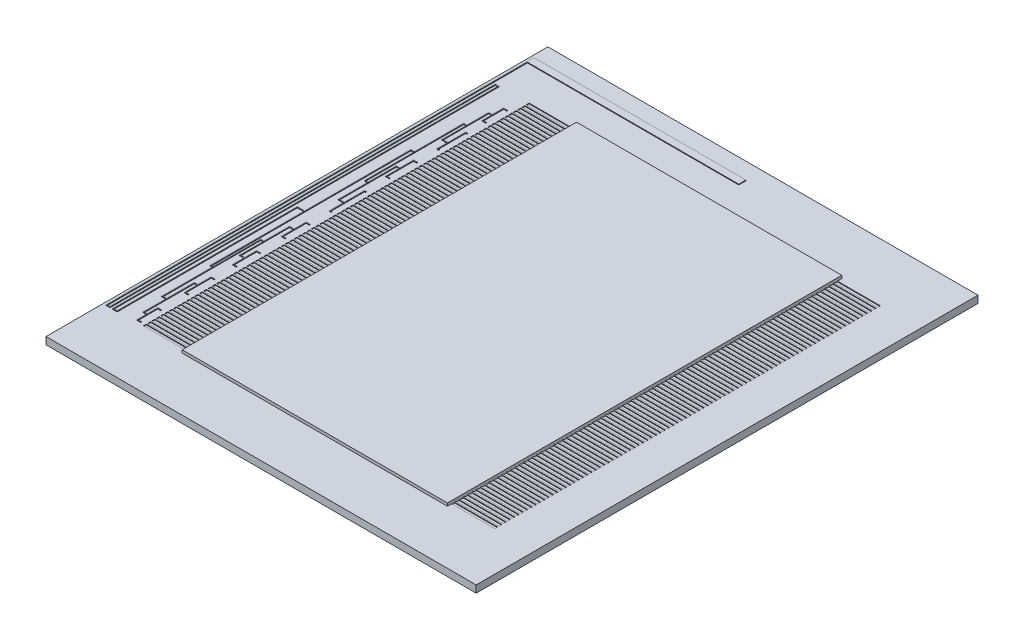
SolidWorks part; units mm, degrees
ref_plane "Front Plane" through (0, 0, 0) normal (0, 0, 1) x (1, 0, 0)
ref_plane "Top Plane" through (0, 0, 0) normal (0, 1, 0) x (1, 0, 0)
ref_plane "Right Plane" through (0, 0, 0) normal (1, 0, 0) x (0, 0, -1)
sketch "Sketch2" plane through (0, 0, 0) normal (0, 1, 0) x (1, 0, 0)
  line L1 (-15, 17.5) -> (15, 17.5)
  line L2 (-15, 17.5) -> (-15, -17.5)
  line L3 (-15, -17.5) -> (15, -17.5)
  line L4 (15, 17.5) -> (15, -17.5)
  line L5 (-15, 17.5) -> (15, -17.5) construction
  line L6 (-15, -17.5) -> (15, 17.5) construction
  point P0 (0, 0)
  dimension "D1" = 35
  dimension "D2" = 30
extrude "Boss-Extrude1" add sketch "Sketch2" against normal blind 0.5
sketch "Sketch3" plane through (0, 0, 0) normal (0, 1, 0) x (1, 0, 0)
  line L1 (-9.25, 13.75) -> (9.25, 13.75)
  line L2 (-9.25, 13.75) -> (-9.25, -13.75)
  line L3 (-9.25, -13.75) -> (9.25, -13.75)
  line L4 (9.25, 13.75) -> (9.25, -13.75)
  line L5 (-9.25, 13.75) -> (9.25, -13.75) construction
  line L6 (-9.25, -13.75) -> (9.25, 13.75) construction
  point P0 (0, 0)
  dimension "D1" = 18.5
  dimension "D2" = 27.5
sketch "Sketch4" plane through (0, 0, 0) normal (0, 1, 0) x (1, 0, 0)
  line L0 (9.25, 13.45) -> (9.25, 13.25)
  line L1 (9.25, 13.45) -> (12.25, 13.45)
  line L2 (9.25, 13.25) -> (12.25, 13.25)
  line L3 (12.25, 13.45) -> (12.25, 13.25)
  line L4 (9.25, 13.75) -> (9.25, -13.75) construction
  line L5 (9.25, 13.15) -> (9.25, 12.95)
  line L6 (9.25, 13.15) -> (12.25, 13.15)
  line L7 (12.25, 13.15) -> (12.25, 12.95)
  line L8 (9.25, 12.95) -> (12.25, 12.95)
  line L9 (9.25, 12.85) -> (9.25, 12.65)
  line L10 (9.25, 12.85) -> (12.25, 12.85)
  line L11 (12.25, 12.85) -> (12.25, 12.65)
  line L12 (9.25, 12.65) -> (12.25, 12.65)
  line L13 (9.25, 12.55) -> (9.25, 12.35)
  line L14 (9.25, 12.55) -> (12.25, 12.55)
  line L15 (12.25, 12.55) -> (12.25, 12.35)
  line L16 (9.25, 12.35) -> (12.25, 12.35)
  line L17 (9.25, 12.25) -> (9.25, 12.05)
  line L18 (9.25, 12.25) -> (12.25, 12.25)
  line L19 (12.25, 12.25) -> (12.25, 12.05)
  line L20 (9.25, 12.05) -> (12.25, 12.05)
  line L21 (9.25, 11.95) -> (9.25, 11.75)
  line L22 (9.25, 11.95) -> (12.25, 11.95)
  line L23 (12.25, 11.95) -> (12.25, 11.75)
  line L24 (9.25, 11.75) -> (12.25, 11.75)
  line L25 (9.25, 11.65) -> (9.25, 11.45)
  line L26 (9.25, 11.65) -> (12.25, 11.65)
  line L27 (12.25, 11.65) -> (12.25, 11.45)
  line L28 (9.25, 11.45) -> (12.25, 11.45)
  line L29 (9.25, 11.35) -> (9.25, 11.15)
  line L30 (9.25, 11.35) -> (12.25, 11.35)
  line L31 (12.25, 11.35) -> (12.25, 11.15)
  line L32 (9.25, 11.15) -> (12.25, 11.15)
  line L33 (9.25, 11.05) -> (9.25, 10.85)
  line L34 (9.25, 11.05) -> (12.25, 11.05)
  line L35 (12.25, 11.05) -> (12.25, 10.85)
  line L36 (9.25, 10.85) -> (12.25, 10.85)
  line L37 (9.25, 10.75) -> (9.25, 10.55)
  line L38 (9.25, 10.75) -> (12.25, 10.75)
  line L39 (12.25, 10.75) -> (12.25, 10.55)
  line L40 (9.25, 10.55) -> (12.25, 10.55)
  line L41 (9.25, 10.45) -> (9.25, 10.25)
  line L42 (9.25, 10.45) -> (12.25, 10.45)
  line L43 (12.25, 10.45) -> (12.25, 10.25)
  line L44 (9.25, 10.25) -> (12.25, 10.25)
  line L45 (9.25, 10.15) -> (9.25, 9.95)
  line L46 (9.25, 10.15) -> (12.25, 10.15)
  line L47 (12.25, 10.15) -> (12.25, 9.95)
  line L48 (9.25, 9.95) -> (12.25, 9.95)
  line L49 (9.25, 9.85) -> (9.25, 9.65)
  line L50 (9.25, 9.85) -> (12.25, 9.85)
  line L51 (12.25, 9.85) -> (12.25, 9.65)
  line L52 (9.25, 9.65) -> (12.25, 9.65)
  line L53 (9.25, 9.55) -> (9.25, 9.35)
  line L54 (9.25, 9.55) -> (12.25, 9.55)
  line L55 (12.25, 9.55) -> (12.25, 9.35)
  line L56 (9.25, 9.35) -> (12.25, 9.35)
  line L57 (9.25, 9.25) -> (9.25, 9.05)
  line L58 (9.25, 9.25) -> (12.25, 9.25)
  line L59 (12.25, 9.25) -> (12.25, 9.05)
  line L60 (9.25, 9.05) -> (12.25, 9.05)
  line L61 (9.25, 8.95) -> (9.25, 8.75)
  line L62 (9.25, 8.95) -> (12.25, 8.95)
  line L63 (12.25, 8.95) -> (12.25, 8.75)
  line L64 (9.25, 8.75) -> (12.25, 8.75)
  line L65 (9.25, 8.65) -> (9.25, 8.45)
  line L66 (9.25, 8.65) -> (12.25, 8.65)
  line L67 (12.25, 8.65) -> (12.25, 8.45)
  line L68 (9.25, 8.45) -> (12.25, 8.45)
  line L69 (9.25, 8.35) -> (9.25, 8.15)
  line L70 (9.25, 8.35) -> (12.25, 8.35)
  line L71 (12.25, 8.35) -> (12.25, 8.15)
  line L72 (9.25, 8.15) -> (12.25, 8.15)
  line L73 (9.25, 8.05) -> (9.25, 7.85)
  line L74 (9.25, 8.05) -> (12.25, 8.05)
  line L75 (12.25, 8.05) -> (12.25, 7.85)
  line L76 (9.25, 7.85) -> (12.25, 7.85)
  line L77 (9.25, 7.75) -> (9.25, 7.55)
  line L78 (9.25, 7.75) -> (12.25, 7.75)
  line L79 (12.25, 7.75) -> (12.25, 7.55)
  line L80 (9.25, 7.55) -> (12.25, 7.55)
  line L81 (9.25, 7.45) -> (9.25, 7.25)
  line L82 (9.25, 7.45) -> (12.25, 7.45)
  line L83 (12.25, 7.45) -> (12.25, 7.25)
  line L84 (9.25, 7.25) -> (12.25, 7.25)
  line L85 (9.25, 7.15) -> (9.25, 6.95)
  line L86 (9.25, 7.15) -> (12.25, 7.15)
  line L87 (12.25, 7.15) -> (12.25, 6.95)
  line L88 (9.25, 6.95) -> (12.25, 6.95)
  line L89 (9.25, 6.85) -> (9.25, 6.65)
  line L90 (9.25, 6.85) -> (12.25, 6.85)
  line L91 (12.25, 6.85) -> (12.25, 6.65)
  line L92 (9.25, 6.65) -> (12.25, 6.65)
  line L93 (9.25, 6.55) -> (9.25, 6.35)
  line L94 (9.25, 6.55) -> (12.25, 6.55)
  line L95 (12.25, 6.55) -> (12.25, 6.35)
  line L96 (9.25, 6.35) -> (12.25, 6.35)
  line L97 (9.25, 6.25) -> (9.25, 6.05)
  line L98 (9.25, 6.25) -> (12.25, 6.25)
  line L99 (12.25, 6.25) -> (12.25, 6.05)
  line L100 (9.25, 6.05) -> (12.25, 6.05)
  line L101 (9.25, 5.95) -> (9.25, 5.75)
  line L102 (9.25, 5.95) -> (12.25, 5.95)
  line L103 (12.25, 5.95) -> (12.25, 5.75)
  line L104 (9.25, 5.75) -> (12.25, 5.75)
  line L105 (9.25, 5.65) -> (9.25, 5.45)
  line L106 (9.25, 5.65) -> (12.25, 5.65)
  line L107 (12.25, 5.65) -> (12.25, 5.45)
  line L108 (9.25, 5.45) -> (12.25, 5.45)
  line L109 (9.25, 5.35) -> (9.25, 5.15)
  line L110 (9.25, 5.35) -> (12.25, 5.35)
  line L111 (12.25, 5.35) -> (12.25, 5.15)
  line L112 (9.25, 5.15) -> (12.25, 5.15)
  line L113 (9.25, 5.05) -> (9.25, 4.85)
  line L114 (9.25, 5.05) -> (12.25, 5.05)
  line L115 (12.25, 5.05) -> (12.25, 4.85)
  line L116 (9.25, 4.85) -> (12.25, 4.85)
  line L117 (9.25, 4.75) -> (9.25, 4.55)
  line L118 (9.25, 4.75) -> (12.25, 4.75)
  line L119 (12.25, 4.75) -> (12.25, 4.55)
  line L120 (9.25, 4.55) -> (12.25, 4.55)
  line L121 (9.25, 4.45) -> (9.25, 4.25)
  line L122 (9.25, 4.45) -> (12.25, 4.45)
  line L123 (12.25, 4.45) -> (12.25, 4.25)
  line L124 (9.25, 4.25) -> (12.25, 4.25)
  line L125 (9.25, 4.15) -> (9.25, 3.95)
  line L126 (9.25, 4.15) -> (12.25, 4.15)
  line L127 (12.25, 4.15) -> (12.25, 3.95)
  line L128 (9.25, 3.95) -> (12.25, 3.95)
  line L129 (9.25, 3.85) -> (9.25, 3.65)
  line L130 (9.25, 3.85) -> (12.25, 3.85)
  line L131 (12.25, 3.85) -> (12.25, 3.65)
  line L132 (9.25, 3.65) -> (12.25, 3.65)
  line L133 (9.25, 3.55) -> (9.25, 3.35)
  line L134 (9.25, 3.55) -> (12.25, 3.55)
  line L135 (12.25, 3.55) -> (12.25, 3.35)
  line L136 (9.25, 3.35) -> (12.25, 3.35)
  line L137 (9.25, 3.25) -> (9.25, 3.05)
  line L138 (9.25, 3.25) -> (12.25, 3.25)
  line L139 (12.25, 3.25) -> (12.25, 3.05)
  line L140 (9.25, 3.05) -> (12.25, 3.05)
  line L141 (9.25, 2.95) -> (9.25, 2.75)
  line L142 (9.25, 2.95) -> (12.25, 2.95)
  line L143 (12.25, 2.95) -> (12.25, 2.75)
  line L144 (9.25, 2.75) -> (12.25, 2.75)
  line L145 (9.25, 2.65) -> (9.25, 2.45)
  line L146 (9.25, 2.65) -> (12.25, 2.65)
  line L147 (12.25, 2.65) -> (12.25, 2.45)
  line L148 (9.25, 2.45) -> (12.25, 2.45)
  line L149 (9.25, 2.35) -> (9.25, 2.15)
  line L150 (9.25, 2.35) -> (12.25, 2.35)
  line L151 (12.25, 2.35) -> (12.25, 2.15)
  line L152 (9.25, 2.15) -> (12.25, 2.15)
  line L153 (9.25, 2.05) -> (9.25, 1.85)
  line L154 (9.25, 2.05) -> (12.25, 2.05)
  line L155 (12.25, 2.05) -> (12.25, 1.85)
  line L156 (9.25, 1.85) -> (12.25, 1.85)
  line L157 (9.25, 1.75) -> (9.25, 1.55)
  line L158 (9.25, 1.75) -> (12.25, 1.75)
  line L159 (12.25, 1.75) -> (12.25, 1.55)
  line L160 (9.25, 1.55) -> (12.25, 1.55)
  line L161 (9.25, 1.45) -> (9.25, 1.25)
  line L162 (9.25, 1.45) -> (12.25, 1.45)
  line L163 (12.25, 1.45) -> (12.25, 1.25)
  line L164 (9.25, 1.25) -> (12.25, 1.25)
  line L165 (9.25, 1.15) -> (9.25, 0.95)
  line L166 (9.25, 1.15) -> (12.25, 1.15)
  line L167 (12.25, 1.15) -> (12.25, 0.95)
  line L168 (9.25, 0.95) -> (12.25, 0.95)
  line L169 (9.25, 0.85) -> (9.25, 0.65)
  line L170 (9.25, 0.85) -> (12.25, 0.85)
  line L171 (12.25, 0.85) -> (12.25, 0.65)
  line L172 (9.25, 0.65) -> (12.25, 0.65)
  line L173 (9.25, 0.55) -> (9.25, 0.35)
  line L174 (9.25, 0.55) -> (12.25, 0.55)
  line L175 (12.25, 0.55) -> (12.25, 0.35)
  line L176 (9.25, 0.35) -> (12.25, 0.35)
  line L177 (9.25, 0.25) -> (9.25, 0.05)
  line L178 (9.25, 0.25) -> (12.25, 0.25)
  line L179 (12.25, 0.25) -> (12.25, 0.05)
  line L180 (9.25, 0.05) -> (12.25, 0.05)
  line L181 (9.25, -0.05) -> (9.25, -0.25)
  line L182 (9.25, -0.05) -> (12.25, -0.05)
  line L183 (12.25, -0.05) -> (12.25, -0.25)
  line L184 (9.25, -0.25) -> (12.25, -0.25)
  line L185 (9.25, -0.35) -> (9.25, -0.55)
  line L186 (9.25, -0.35) -> (12.25, -0.35)
  line L187 (12.25, -0.35) -> (12.25, -0.55)
  line L188 (9.25, -0.55) -> (12.25, -0.55)
  line L189 (9.25, -0.65) -> (9.25, -0.85)
  line L190 (9.25, -0.65) -> (12.25, -0.65)
  line L191 (12.25, -0.65) -> (12.25, -0.85)
  line L192 (9.25, -0.85) -> (12.25, -0.85)
  line L193 (9.25, -0.95) -> (9.25, -1.15)
  line L194 (9.25, -0.95) -> (12.25, -0.95)
  line L195 (12.25, -0.95) -> (12.25, -1.15)
  line L196 (9.25, -1.15) -> (12.25, -1.15)
  line L197 (9.25, -1.25) -> (9.25, -1.45)
  line L198 (9.25, -1.25) -> (12.25, -1.25)
  line L199 (12.25, -1.25) -> (12.25, -1.45)
  line L200 (9.25, -1.45) -> (12.25, -1.45)
  line L201 (9.25, -1.55) -> (9.25, -1.75)
  line L202 (9.25, -1.55) -> (12.25, -1.55)
  line L203 (12.25, -1.55) -> (12.25, -1.75)
  line L204 (9.25, -1.75) -> (12.25, -1.75)
  line L205 (9.25, -1.85) -> (9.25, -2.05)
  line L206 (9.25, -1.85) -> (12.25, -1.85)
  line L207 (12.25, -1.85) -> (12.25, -2.05)
  line L208 (9.25, -2.05) -> (12.25, -2.05)
  line L209 (9.25, -2.15) -> (9.25, -2.35)
  line L210 (9.25, -2.15) -> (12.25, -2.15)
  line L211 (12.25, -2.15) -> (12.25, -2.35)
  line L212 (9.25, -2.35) -> (12.25, -2.35)
  line L213 (9.25, -2.45) -> (9.25, -2.65)
  line L214 (9.25, -2.45) -> (12.25, -2.45)
  line L215 (12.25, -2.45) -> (12.25, -2.65)
  line L216 (9.25, -2.65) -> (12.25, -2.65)
  line L217 (9.25, -2.75) -> (9.25, -2.95)
  line L218 (9.25, -2.75) -> (12.25, -2.75)
  line L219 (12.25, -2.75) -> (12.25, -2.95)
  line L220 (9.25, -2.95) -> (12.25, -2.95)
  line L221 (9.25, -3.05) -> (9.25, -3.25)
  line L222 (9.25, -3.05) -> (12.25, -3.05)
  line L223 (12.25, -3.05) -> (12.25, -3.25)
  line L224 (9.25, -3.25) -> (12.25, -3.25)
  line L225 (9.25, -3.35) -> (9.25, -3.55)
  line L226 (9.25, -3.35) -> (12.25, -3.35)
  line L227 (12.25, -3.35) -> (12.25, -3.55)
  line L228 (9.25, -3.55) -> (12.25, -3.55)
  line L229 (9.25, -3.65) -> (9.25, -3.85)
  line L230 (9.25, -3.65) -> (12.25, -3.65)
  line L231 (12.25, -3.65) -> (12.25, -3.85)
  line L232 (9.25, -3.85) -> (12.25, -3.85)
  line L233 (9.25, -3.95) -> (9.25, -4.15)
  line L234 (9.25, -3.95) -> (12.25, -3.95)
  line L235 (12.25, -3.95) -> (12.25, -4.15)
  line L236 (9.25, -4.15) -> (12.25, -4.15)
  line L237 (9.25, -4.25) -> (9.25, -4.45)
  line L238 (9.25, -4.25) -> (12.25, -4.25)
  line L239 (12.25, -4.25) -> (12.25, -4.45)
  line L240 (9.25, -4.45) -> (12.25, -4.45)
  line L241 (9.25, -4.55) -> (9.25, -4.75)
  line L242 (9.25, -4.55) -> (12.25, -4.55)
  line L243 (12.25, -4.55) -> (12.25, -4.75)
  line L244 (9.25, -4.75) -> (12.25, -4.75)
  line L245 (9.25, -4.85) -> (9.25, -5.05)
  line L246 (9.25, -4.85) -> (12.25, -4.85)
  line L247 (12.25, -4.85) -> (12.25, -5.05)
  line L248 (9.25, -5.05) -> (12.25, -5.05)
  line L249 (9.25, -5.15) -> (9.25, -5.35)
  line L250 (9.25, -5.15) -> (12.25, -5.15)
  line L251 (12.25, -5.15) -> (12.25, -5.35)
  line L252 (9.25, -5.35) -> (12.25, -5.35)
  line L253 (9.25, -5.45) -> (9.25, -5.65)
  line L254 (9.25, -5.45) -> (12.25, -5.45)
  line L255 (12.25, -5.45) -> (12.25, -5.65)
  line L256 (9.25, -5.65) -> (12.25, -5.65)
  line L257 (9.25, -5.75) -> (9.25, -5.95)
  line L258 (9.25, -5.75) -> (12.25, -5.75)
  line L259 (12.25, -5.75) -> (12.25, -5.95)
  line L260 (9.25, -5.95) -> (12.25, -5.95)
  line L261 (9.25, -6.05) -> (9.25, -6.25)
  line L262 (9.25, -6.05) -> (12.25, -6.05)
  line L263 (12.25, -6.05) -> (12.25, -6.25)
  line L264 (9.25, -6.25) -> (12.25, -6.25)
  line L265 (9.25, -6.35) -> (9.25, -6.55)
  line L266 (9.25, -6.35) -> (12.25, -6.35)
  line L267 (12.25, -6.35) -> (12.25, -6.55)
  line L268 (9.25, -6.55) -> (12.25, -6.55)
  line L269 (9.25, -6.65) -> (9.25, -6.85)
  line L270 (9.25, -6.65) -> (12.25, -6.65)
  line L271 (12.25, -6.65) -> (12.25, -6.85)
  line L272 (9.25, -6.85) -> (12.25, -6.85)
  line L273 (9.25, -6.95) -> (9.25, -7.15)
  line L274 (9.25, -6.95) -> (12.25, -6.95)
  line L275 (12.25, -6.95) -> (12.25, -7.15)
  line L276 (9.25, -7.15) -> (12.25, -7.15)
  line L277 (9.25, -7.25) -> (9.25, -7.45)
  line L278 (9.25, -7.25) -> (12.25, -7.25)
  line L279 (12.25, -7.25) -> (12.25, -7.45)
  line L280 (9.25, -7.45) -> (12.25, -7.45)
  line L281 (9.25, -7.55) -> (9.25, -7.75)
  line L282 (9.25, -7.55) -> (12.25, -7.55)
  line L283 (12.25, -7.55) -> (12.25, -7.75)
  line L284 (9.25, -7.75) -> (12.25, -7.75)
  line L285 (9.25, -7.85) -> (9.25, -8.05)
  line L286 (9.25, -7.85) -> (12.25, -7.85)
  line L287 (12.25, -7.85) -> (12.25, -8.05)
  line L288 (9.25, -8.05) -> (12.25, -8.05)
  line L289 (9.25, -8.15) -> (9.25, -8.35)
  line L290 (9.25, -8.15) -> (12.25, -8.15)
  line L291 (12.25, -8.15) -> (12.25, -8.35)
  line L292 (9.25, -8.35) -> (12.25, -8.35)
  line L293 (9.25, -8.45) -> (9.25, -8.65)
  line L294 (9.25, -8.45) -> (12.25, -8.45)
  line L295 (12.25, -8.45) -> (12.25, -8.65)
  line L296 (9.25, -8.65) -> (12.25, -8.65)
  line L297 (9.25, -8.75) -> (9.25, -8.95)
  line L298 (9.25, -8.75) -> (12.25, -8.75)
  line L299 (12.25, -8.75) -> (12.25, -8.95)
  line L300 (9.25, -8.95) -> (12.25, -8.95)
  line L301 (9.25, -9.05) -> (9.25, -9.25)
  line L302 (9.25, -9.05) -> (12.25, -9.05)
  line L303 (12.25, -9.05) -> (12.25, -9.25)
  line L304 (9.25, -9.25) -> (12.25, -9.25)
  line L305 (9.25, -9.35) -> (9.25, -9.55)
  line L306 (9.25, -9.35) -> (12.25, -9.35)
  line L307 (12.25, -9.35) -> (12.25, -9.55)
  line L308 (9.25, -9.55) -> (12.25, -9.55)
  line L309 (9.25, -9.65) -> (9.25, -9.85)
  line L310 (9.25, -9.65) -> (12.25, -9.65)
  line L311 (12.25, -9.65) -> (12.25, -9.85)
  line L312 (9.25, -9.85) -> (12.25, -9.85)
  line L313 (9.25, -9.95) -> (9.25, -10.15)
  line L314 (9.25, -9.95) -> (12.25, -9.95)
  line L315 (12.25, -9.95) -> (12.25, -10.15)
  line L316 (9.25, -10.15) -> (12.25, -10.15)
  line L317 (9.25, -10.25) -> (9.25, -10.45)
  line L318 (9.25, -10.25) -> (12.25, -10.25)
  line L319 (12.25, -10.25) -> (12.25, -10.45)
  line L320 (9.25, -10.45) -> (12.25, -10.45)
  line L321 (9.25, -10.55) -> (9.25, -10.75)
  line L322 (9.25, -10.55) -> (12.25, -10.55)
  line L323 (12.25, -10.55) -> (12.25, -10.75)
  line L324 (9.25, -10.75) -> (12.25, -10.75)
  line L325 (9.25, -10.85) -> (9.25, -11.05)
  line L326 (9.25, -10.85) -> (12.25, -10.85)
  line L327 (12.25, -10.85) -> (12.25, -11.05)
  line L328 (9.25, -11.05) -> (12.25, -11.05)
  line L329 (9.25, -11.15) -> (9.25, -11.35)
  line L330 (9.25, -11.15) -> (12.25, -11.15)
  line L331 (12.25, -11.15) -> (12.25, -11.35)
  line L332 (9.25, -11.35) -> (12.25, -11.35)
  line L333 (9.25, -11.45) -> (9.25, -11.65)
  line L334 (9.25, -11.45) -> (12.25, -11.45)
  line L335 (12.25, -11.45) -> (12.25, -11.65)
  line L336 (9.25, -11.65) -> (12.25, -11.65)
  line L337 (9.25, -11.75) -> (9.25, -11.95)
  line L338 (9.25, -11.75) -> (12.25, -11.75)
  line L339 (12.25, -11.75) -> (12.25, -11.95)
  line L340 (9.25, -11.95) -> (12.25, -11.95)
  line L341 (9.25, -12.05) -> (9.25, -12.25)
  line L342 (9.25, -12.05) -> (12.25, -12.05)
  line L343 (12.25, -12.05) -> (12.25, -12.25)
  line L344 (9.25, -12.25) -> (12.25, -12.25)
  line L345 (9.25, -12.35) -> (9.25, -12.55)
  line L346 (9.25, -12.35) -> (12.25, -12.35)
  line L347 (12.25, -12.35) -> (12.25, -12.55)
  line L348 (9.25, -12.55) -> (12.25, -12.55)
  line L349 (9.25, -12.65) -> (9.25, -12.85)
  line L350 (9.25, -12.65) -> (12.25, -12.65)
  line L351 (12.25, -12.65) -> (12.25, -12.85)
  line L352 (9.25, -12.85) -> (12.25, -12.85)
  line L353 (9.25, -12.95) -> (9.25, -13.15)
  line L354 (9.25, -12.95) -> (12.25, -12.95)
  line L355 (12.25, -12.95) -> (12.25, -13.15)
  line L356 (9.25, -13.15) -> (12.25, -13.15)
  line L357 (9.25, -13.25) -> (9.25, -13.45)
  line L358 (9.25, -13.25) -> (12.25, -13.25)
  line L359 (12.25, -13.25) -> (12.25, -13.45)
  line L360 (9.25, -13.45) -> (12.25, -13.45)
  line L361 (-9.25, 13.45) -> (-9.25, 13.25)
  line L362 (-9.25, 13.45) -> (-12.25, 13.45)
  line L363 (-9.25, 13.25) -> (-12.25, 13.25)
  line L364 (-12.25, 13.45) -> (-12.25, 13.25)
  line L365 (-9.25, 13.75) -> (-9.25, -13.75) construction
  line L366 (-9.25, 13.15) -> (-9.25, 12.95)
  line L367 (-9.25, 13.15) -> (-12.25, 13.15)
  line L368 (-12.25, 13.15) -> (-12.25, 12.95)
  line L369 (-9.25, 12.95) -> (-12.25, 12.95)
  line L370 (-9.25, 12.85) -> (-9.25, 12.65)
  line L371 (-9.25, 12.85) -> (-12.25, 12.85)
  line L372 (-12.25, 12.85) -> (-12.25, 12.65)
  line L373 (-9.25, 12.65) -> (-12.25, 12.65)
  line L374 (-9.25, 12.55) -> (-9.25, 12.35)
  line L375 (-9.25, 12.55) -> (-12.25, 12.55)
  line L376 (-12.25, 12.55) -> (-12.25, 12.35)
  line L377 (-9.25, 12.35) -> (-12.25, 12.35)
  line L378 (-9.25, 12.25) -> (-9.25, 12.05)
  line L379 (-9.25, 12.25) -> (-12.25, 12.25)
  line L380 (-12.25, 12.25) -> (-12.25, 12.05)
  line L381 (-9.25, 12.05) -> (-12.25, 12.05)
  line L382 (-9.25, 11.95) -> (-9.25, 11.75)
  line L383 (-9.25, 11.95) -> (-12.25, 11.95)
  line L384 (-12.25, 11.95) -> (-12.25, 11.75)
  line L385 (-9.25, 11.75) -> (-12.25, 11.75)
  line L386 (-9.25, 11.65) -> (-9.25, 11.45)
  line L387 (-9.25, 11.65) -> (-12.25, 11.65)
  line L388 (-12.25, 11.65) -> (-12.25, 11.45)
  line L389 (-9.25, 11.45) -> (-12.25, 11.45)
  line L390 (-9.25, 11.35) -> (-9.25, 11.15)
  line L391 (-9.25, 11.35) -> (-12.25, 11.35)
  line L392 (-12.25, 11.35) -> (-12.25, 11.15)
  line L393 (-9.25, 11.15) -> (-12.25, 11.15)
  line L394 (-9.25, 11.05) -> (-9.25, 10.85)
  line L395 (-9.25, 11.05) -> (-12.25, 11.05)
  line L396 (-12.25, 11.05) -> (-12.25, 10.85)
  line L397 (-9.25, 10.85) -> (-12.25, 10.85)
  line L398 (-9.25, 10.75) -> (-9.25, 10.55)
  line L399 (-9.25, 10.75) -> (-12.25, 10.75)
  line L400 (-12.25, 10.75) -> (-12.25, 10.55)
  line L401 (-9.25, 10.55) -> (-12.25, 10.55)
  line L402 (-9.25, 10.45) -> (-9.25, 10.25)
  line L403 (-9.25, 10.45) -> (-12.25, 10.45)
  line L404 (-12.25, 10.45) -> (-12.25, 10.25)
  line L405 (-9.25, 10.25) -> (-12.25, 10.25)
  line L406 (-9.25, 10.15) -> (-9.25, 9.95)
  line L407 (-9.25, 10.15) -> (-12.25, 10.15)
  line L408 (-12.25, 10.15) -> (-12.25, 9.95)
  line L409 (-9.25, 9.95) -> (-12.25, 9.95)
  line L410 (-9.25, 9.85) -> (-9.25, 9.65)
  line L411 (-9.25, 9.85) -> (-12.25, 9.85)
  line L412 (-12.25, 9.85) -> (-12.25, 9.65)
  line L413 (-9.25, 9.65) -> (-12.25, 9.65)
  line L414 (-9.25, 9.55) -> (-9.25, 9.35)
  line L415 (-9.25, 9.55) -> (-12.25, 9.55)
  line L416 (-12.25, 9.55) -> (-12.25, 9.35)
  line L417 (-9.25, 9.35) -> (-12.25, 9.35)
  line L418 (-9.25, 9.25) -> (-9.25, 9.05)
  line L419 (-9.25, 9.25) -> (-12.25, 9.25)
  line L420 (-12.25, 9.25) -> (-12.25, 9.05)
  line L421 (-9.25, 9.05) -> (-12.25, 9.05)
  line L422 (-9.25, 8.95) -> (-9.25, 8.75)
  line L423 (-9.25, 8.95) -> (-12.25, 8.95)
  line L424 (-12.25, 8.95) -> (-12.25, 8.75)
  line L425 (-9.25, 8.75) -> (-12.25, 8.75)
  line L426 (-9.25, 8.65) -> (-9.25, 8.45)
  line L427 (-9.25, 8.65) -> (-12.25, 8.65)
  line L428 (-12.25, 8.65) -> (-12.25, 8.45)
  line L429 (-9.25, 8.45) -> (-12.25, 8.45)
  line L430 (-9.25, 8.35) -> (-9.25, 8.15)
  line L431 (-9.25, 8.35) -> (-12.25, 8.35)
  line L432 (-12.25, 8.35) -> (-12.25, 8.15)
  line L433 (-9.25, 8.15) -> (-12.25, 8.15)
  line L434 (-9.25, 8.05) -> (-9.25, 7.85)
  line L435 (-9.25, 8.05) -> (-12.25, 8.05)
  line L436 (-12.25, 8.05) -> (-12.25, 7.85)
  line L437 (-9.25, 7.85) -> (-12.25, 7.85)
  line L438 (-9.25, 7.75) -> (-9.25, 7.55)
  line L439 (-9.25, 7.75) -> (-12.25, 7.75)
  line L440 (-12.25, 7.75) -> (-12.25, 7.55)
  line L441 (-9.25, 7.55) -> (-12.25, 7.55)
  line L442 (-9.25, 7.45) -> (-9.25, 7.25)
  line L443 (-9.25, 7.45) -> (-12.25, 7.45)
  line L444 (-12.25, 7.45) -> (-12.25, 7.25)
  line L445 (-9.25, 7.25) -> (-12.25, 7.25)
  line L446 (-9.25, 7.15) -> (-9.25, 6.95)
  line L447 (-9.25, 7.15) -> (-12.25, 7.15)
  line L448 (-12.25, 7.15) -> (-12.25, 6.95)
  line L449 (-9.25, 6.95) -> (-12.25, 6.95)
  line L450 (-9.25, 6.85) -> (-9.25, 6.65)
  line L451 (-9.25, 6.85) -> (-12.25, 6.85)
  line L452 (-12.25, 6.85) -> (-12.25, 6.65)
  line L453 (-9.25, 6.65) -> (-12.25, 6.65)
  line L454 (-9.25, 6.55) -> (-9.25, 6.35)
  line L455 (-9.25, 6.55) -> (-12.25, 6.55)
  line L456 (-12.25, 6.55) -> (-12.25, 6.35)
  line L457 (-9.25, 6.35) -> (-12.25, 6.35)
  line L458 (-9.25, 6.25) -> (-9.25, 6.05)
  line L459 (-9.25, 6.25) -> (-12.25, 6.25)
  line L460 (-12.25, 6.25) -> (-12.25, 6.05)
  line L461 (-9.25, 6.05) -> (-12.25, 6.05)
  line L462 (-9.25, 5.95) -> (-9.25, 5.75)
  line L463 (-9.25, 5.95) -> (-12.25, 5.95)
  line L464 (-12.25, 5.95) -> (-12.25, 5.75)
  line L465 (-9.25, 5.75) -> (-12.25, 5.75)
  line L466 (-9.25, 5.65) -> (-9.25, 5.45)
  line L467 (-9.25, 5.65) -> (-12.25, 5.65)
  line L468 (-12.25, 5.65) -> (-12.25, 5.45)
  line L469 (-9.25, 5.45) -> (-12.25, 5.45)
  line L470 (-9.25, 5.35) -> (-9.25, 5.15)
  line L471 (-9.25, 5.35) -> (-12.25, 5.35)
  line L472 (-12.25, 5.35) -> (-12.25, 5.15)
  line L473 (-9.25, 5.15) -> (-12.25, 5.15)
  line L474 (-9.25, 5.05) -> (-9.25, 4.85)
  line L475 (-9.25, 5.05) -> (-12.25, 5.05)
  line L476 (-12.25, 5.05) -> (-12.25, 4.85)
  line L477 (-9.25, 4.85) -> (-12.25, 4.85)
  line L478 (-9.25, 4.75) -> (-9.25, 4.55)
  line L479 (-9.25, 4.75) -> (-12.25, 4.75)
  line L480 (-12.25, 4.75) -> (-12.25, 4.55)
  line L481 (-9.25, 4.55) -> (-12.25, 4.55)
  line L482 (-9.25, 4.45) -> (-9.25, 4.25)
  line L483 (-9.25, 4.45) -> (-12.25, 4.45)
  line L484 (-12.25, 4.45) -> (-12.25, 4.25)
  line L485 (-9.25, 4.25) -> (-12.25, 4.25)
  line L486 (-9.25, 4.15) -> (-9.25, 3.95)
  line L487 (-9.25, 4.15) -> (-12.25, 4.15)
  line L488 (-12.25, 4.15) -> (-12.25, 3.95)
  line L489 (-9.25, 3.95) -> (-12.25, 3.95)
  line L490 (-9.25, 3.85) -> (-9.25, 3.65)
  line L491 (-9.25, 3.85) -> (-12.25, 3.85)
  line L492 (-12.25, 3.85) -> (-12.25, 3.65)
  line L493 (-9.25, 3.65) -> (-12.25, 3.65)
  line L494 (-9.25, 3.55) -> (-9.25, 3.35)
  line L495 (-9.25, 3.55) -> (-12.25, 3.55)
  line L496 (-12.25, 3.55) -> (-12.25, 3.35)
  line L497 (-9.25, 3.35) -> (-12.25, 3.35)
  line L498 (-9.25, 3.25) -> (-9.25, 3.05)
  line L499 (-9.25, 3.25) -> (-12.25, 3.25)
  line L500 (-12.25, 3.25) -> (-12.25, 3.05)
  line L501 (-9.25, 3.05) -> (-12.25, 3.05)
  line L502 (-9.25, 2.95) -> (-9.25, 2.75)
  line L503 (-9.25, 2.95) -> (-12.25, 2.95)
  line L504 (-12.25, 2.95) -> (-12.25, 2.75)
  line L505 (-9.25, 2.75) -> (-12.25, 2.75)
  line L506 (-9.25, 2.65) -> (-9.25, 2.45)
  line L507 (-9.25, 2.65) -> (-12.25, 2.65)
  line L508 (-12.25, 2.65) -> (-12.25, 2.45)
  line L509 (-9.25, 2.45) -> (-12.25, 2.45)
  line L510 (-9.25, 2.35) -> (-9.25, 2.15)
  line L511 (-9.25, 2.35) -> (-12.25, 2.35)
  line L512 (-12.25, 2.35) -> (-12.25, 2.15)
  line L513 (-9.25, 2.15) -> (-12.25, 2.15)
  line L514 (-9.25, 2.05) -> (-9.25, 1.85)
  line L515 (-9.25, 2.05) -> (-12.25, 2.05)
  line L516 (-12.25, 2.05) -> (-12.25, 1.85)
  line L517 (-9.25, 1.85) -> (-12.25, 1.85)
  line L518 (-9.25, 1.75) -> (-9.25, 1.55)
  line L519 (-9.25, 1.75) -> (-12.25, 1.75)
  line L520 (-12.25, 1.75) -> (-12.25, 1.55)
  line L521 (-9.25, 1.55) -> (-12.25, 1.55)
  line L522 (-9.25, 1.45) -> (-9.25, 1.25)
  line L523 (-9.25, 1.45) -> (-12.25, 1.45)
  line L524 (-12.25, 1.45) -> (-12.25, 1.25)
  line L525 (-9.25, 1.25) -> (-12.25, 1.25)
  line L526 (-9.25, 1.15) -> (-9.25, 0.95)
  line L527 (-9.25, 1.15) -> (-12.25, 1.15)
  line L528 (-12.25, 1.15) -> (-12.25, 0.95)
  line L529 (-9.25, 0.95) -> (-12.25, 0.95)
  line L530 (-9.25, 0.85) -> (-9.25, 0.65)
  line L531 (-9.25, 0.85) -> (-12.25, 0.85)
  line L532 (-12.25, 0.85) -> (-12.25, 0.65)
  line L533 (-9.25, 0.65) -> (-12.25, 0.65)
  line L534 (-9.25, 0.55) -> (-9.25, 0.35)
  line L535 (-9.25, 0.55) -> (-12.25, 0.55)
  line L536 (-12.25, 0.55) -> (-12.25, 0.35)
  line L537 (-9.25, 0.35) -> (-12.25, 0.35)
  line L538 (-9.25, 0.25) -> (-9.25, 0.05)
  line L539 (-9.25, 0.25) -> (-12.25, 0.25)
  line L540 (-12.25, 0.25) -> (-12.25, 0.05)
  line L541 (-9.25, 0.05) -> (-12.25, 0.05)
  line L542 (-9.25, -0.05) -> (-9.25, -0.25)
  line L543 (-9.25, -0.05) -> (-12.25, -0.05)
  line L544 (-12.25, -0.05) -> (-12.25, -0.25)
  line L545 (-9.25, -0.25) -> (-12.25, -0.25)
  line L546 (-9.25, -0.35) -> (-9.25, -0.55)
  line L547 (-9.25, -0.35) -> (-12.25, -0.35)
  line L548 (-12.25, -0.35) -> (-12.25, -0.55)
  line L549 (-9.25, -0.55) -> (-12.25, -0.55)
  line L550 (-9.25, -0.65) -> (-9.25, -0.85)
  line L551 (-9.25, -0.65) -> (-12.25, -0.65)
  line L552 (-12.25, -0.65) -> (-12.25, -0.85)
  line L553 (-9.25, -0.85) -> (-12.25, -0.85)
  line L554 (-9.25, -0.95) -> (-9.25, -1.15)
  line L555 (-9.25, -0.95) -> (-12.25, -0.95)
  line L556 (-12.25, -0.95) -> (-12.25, -1.15)
  line L557 (-9.25, -1.15) -> (-12.25, -1.15)
  line L558 (-9.25, -1.25) -> (-9.25, -1.45)
  line L559 (-9.25, -1.25) -> (-12.25, -1.25)
  line L560 (-12.25, -1.25) -> (-12.25, -1.45)
  line L561 (-9.25, -1.45) -> (-12.25, -1.45)
  line L562 (-9.25, -1.55) -> (-9.25, -1.75)
  line L563 (-9.25, -1.55) -> (-12.25, -1.55)
  line L564 (-12.25, -1.55) -> (-12.25, -1.75)
  line L565 (-9.25, -1.75) -> (-12.25, -1.75)
  line L566 (-9.25, -1.85) -> (-9.25, -2.05)
  line L567 (-9.25, -1.85) -> (-12.25, -1.85)
  line L568 (-12.25, -1.85) -> (-12.25, -2.05)
  line L569 (-9.25, -2.05) -> (-12.25, -2.05)
  line L570 (-9.25, -2.15) -> (-9.25, -2.35)
  line L571 (-9.25, -2.15) -> (-12.25, -2.15)
  line L572 (-12.25, -2.15) -> (-12.25, -2.35)
  line L573 (-9.25, -2.35) -> (-12.25, -2.35)
  line L574 (-9.25, -2.45) -> (-9.25, -2.65)
  line L575 (-9.25, -2.45) -> (-12.25, -2.45)
  line L576 (-12.25, -2.45) -> (-12.25, -2.65)
  line L577 (-9.25, -2.65) -> (-12.25, -2.65)
  line L578 (-9.25, -2.75) -> (-9.25, -2.95)
  line L579 (-9.25, -2.75) -> (-12.25, -2.75)
  line L580 (-12.25, -2.75) -> (-12.25, -2.95)
  line L581 (-9.25, -2.95) -> (-12.25, -2.95)
  line L582 (-9.25, -3.05) -> (-9.25, -3.25)
  line L583 (-9.25, -3.05) -> (-12.25, -3.05)
  line L584 (-12.25, -3.05) -> (-12.25, -3.25)
  line L585 (-9.25, -3.25) -> (-12.25, -3.25)
  line L586 (-9.25, -3.35) -> (-9.25, -3.55)
  line L587 (-9.25, -3.35) -> (-12.25, -3.35)
  line L588 (-12.25, -3.35) -> (-12.25, -3.55)
  line L589 (-9.25, -3.55) -> (-12.25, -3.55)
  line L590 (-9.25, -3.65) -> (-9.25, -3.85)
  line L591 (-9.25, -3.65) -> (-12.25, -3.65)
  line L592 (-12.25, -3.65) -> (-12.25, -3.85)
  line L593 (-9.25, -3.85) -> (-12.25, -3.85)
  line L594 (-9.25, -3.95) -> (-9.25, -4.15)
  line L595 (-9.25, -3.95) -> (-12.25, -3.95)
  line L596 (-12.25, -3.95) -> (-12.25, -4.15)
  line L597 (-9.25, -4.15) -> (-12.25, -4.15)
  line L598 (-9.25, -4.25) -> (-9.25, -4.45)
  line L599 (-9.25, -4.25) -> (-12.25, -4.25)
  line L600 (-12.25, -4.25) -> (-12.25, -4.45)
  line L601 (-9.25, -4.45) -> (-12.25, -4.45)
  line L602 (-9.25, -4.55) -> (-9.25, -4.75)
  line L603 (-9.25, -4.55) -> (-12.25, -4.55)
  line L604 (-12.25, -4.55) -> (-12.25, -4.75)
  line L605 (-9.25, -4.75) -> (-12.25, -4.75)
  line L606 (-9.25, -4.85) -> (-9.25, -5.05)
  line L607 (-9.25, -4.85) -> (-12.25, -4.85)
  line L608 (-12.25, -4.85) -> (-12.25, -5.05)
  line L609 (-9.25, -5.05) -> (-12.25, -5.05)
  line L610 (-9.25, -5.15) -> (-9.25, -5.35)
  line L611 (-9.25, -5.15) -> (-12.25, -5.15)
  line L612 (-12.25, -5.15) -> (-12.25, -5.35)
  line L613 (-9.25, -5.35) -> (-12.25, -5.35)
  line L614 (-9.25, -5.45) -> (-9.25, -5.65)
  line L615 (-9.25, -5.45) -> (-12.25, -5.45)
  line L616 (-12.25, -5.45) -> (-12.25, -5.65)
  line L617 (-9.25, -5.65) -> (-12.25, -5.65)
  line L618 (-9.25, -5.75) -> (-9.25, -5.95)
  line L619 (-9.25, -5.75) -> (-12.25, -5.75)
  line L620 (-12.25, -5.75) -> (-12.25, -5.95)
  line L621 (-9.25, -5.95) -> (-12.25, -5.95)
  line L622 (-9.25, -6.05) -> (-9.25, -6.25)
  line L623 (-9.25, -6.05) -> (-12.25, -6.05)
  line L624 (-12.25, -6.05) -> (-12.25, -6.25)
  line L625 (-9.25, -6.25) -> (-12.25, -6.25)
  line L626 (-9.25, -6.35) -> (-9.25, -6.55)
  line L627 (-9.25, -6.35) -> (-12.25, -6.35)
  line L628 (-12.25, -6.35) -> (-12.25, -6.55)
  line L629 (-9.25, -6.55) -> (-12.25, -6.55)
  line L630 (-9.25, -6.65) -> (-9.25, -6.85)
  line L631 (-9.25, -6.65) -> (-12.25, -6.65)
  line L632 (-12.25, -6.65) -> (-12.25, -6.85)
  line L633 (-9.25, -6.85) -> (-12.25, -6.85)
  line L634 (-9.25, -6.95) -> (-9.25, -7.15)
  line L635 (-9.25, -6.95) -> (-12.25, -6.95)
  line L636 (-12.25, -6.95) -> (-12.25, -7.15)
  line L637 (-9.25, -7.15) -> (-12.25, -7.15)
  line L638 (-9.25, -7.25) -> (-9.25, -7.45)
  line L639 (-9.25, -7.25) -> (-12.25, -7.25)
  line L640 (-12.25, -7.25) -> (-12.25, -7.45)
  line L641 (-9.25, -7.45) -> (-12.25, -7.45)
  line L642 (-9.25, -7.55) -> (-9.25, -7.75)
  line L643 (-9.25, -7.55) -> (-12.25, -7.55)
  line L644 (-12.25, -7.55) -> (-12.25, -7.75)
  line L645 (-9.25, -7.75) -> (-12.25, -7.75)
  line L646 (-9.25, -7.85) -> (-9.25, -8.05)
  line L647 (-9.25, -7.85) -> (-12.25, -7.85)
  line L648 (-12.25, -7.85) -> (-12.25, -8.05)
  line L649 (-9.25, -8.05) -> (-12.25, -8.05)
  line L650 (-9.25, -8.15) -> (-9.25, -8.35)
  line L651 (-9.25, -8.15) -> (-12.25, -8.15)
  line L652 (-12.25, -8.15) -> (-12.25, -8.35)
  line L653 (-9.25, -8.35) -> (-12.25, -8.35)
  line L654 (-9.25, -8.45) -> (-9.25, -8.65)
  line L655 (-9.25, -8.45) -> (-12.25, -8.45)
  line L656 (-12.25, -8.45) -> (-12.25, -8.65)
  line L657 (-9.25, -8.65) -> (-12.25, -8.65)
  line L658 (-9.25, -8.75) -> (-9.25, -8.95)
  line L659 (-9.25, -8.75) -> (-12.25, -8.75)
  line L660 (-12.25, -8.75) -> (-12.25, -8.95)
  line L661 (-9.25, -8.95) -> (-12.25, -8.95)
  line L662 (-9.25, -9.05) -> (-9.25, -9.25)
  line L663 (-9.25, -9.05) -> (-12.25, -9.05)
  line L664 (-12.25, -9.05) -> (-12.25, -9.25)
  line L665 (-9.25, -9.25) -> (-12.25, -9.25)
  line L666 (-9.25, -9.35) -> (-9.25, -9.55)
  line L667 (-9.25, -9.35) -> (-12.25, -9.35)
  line L668 (-12.25, -9.35) -> (-12.25, -9.55)
  line L669 (-9.25, -9.55) -> (-12.25, -9.55)
  line L670 (-9.25, -9.65) -> (-9.25, -9.85)
  line L671 (-9.25, -9.65) -> (-12.25, -9.65)
  line L672 (-12.25, -9.65) -> (-12.25, -9.85)
  line L673 (-9.25, -9.85) -> (-12.25, -9.85)
  line L674 (-9.25, -9.95) -> (-9.25, -10.15)
  line L675 (-9.25, -9.95) -> (-12.25, -9.95)
  line L676 (-12.25, -9.95) -> (-12.25, -10.15)
  line L677 (-9.25, -10.15) -> (-12.25, -10.15)
  line L678 (-9.25, -10.25) -> (-9.25, -10.45)
  line L679 (-9.25, -10.25) -> (-12.25, -10.25)
  line L680 (-12.25, -10.25) -> (-12.25, -10.45)
  line L681 (-9.25, -10.45) -> (-12.25, -10.45)
  line L682 (-9.25, -10.55) -> (-9.25, -10.75)
  line L683 (-9.25, -10.55) -> (-12.25, -10.55)
  line L684 (-12.25, -10.55) -> (-12.25, -10.75)
  line L685 (-9.25, -10.75) -> (-12.25, -10.75)
  line L686 (-9.25, -10.85) -> (-9.25, -11.05)
  line L687 (-9.25, -10.85) -> (-12.25, -10.85)
  line L688 (-12.25, -10.85) -> (-12.25, -11.05)
  line L689 (-9.25, -11.05) -> (-12.25, -11.05)
  line L690 (-9.25, -11.15) -> (-9.25, -11.35)
  line L691 (-9.25, -11.15) -> (-12.25, -11.15)
  line L692 (-12.25, -11.15) -> (-12.25, -11.35)
  line L693 (-9.25, -11.35) -> (-12.25, -11.35)
  line L694 (-9.25, -11.45) -> (-9.25, -11.65)
  line L695 (-9.25, -11.45) -> (-12.25, -11.45)
  line L696 (-12.25, -11.45) -> (-12.25, -11.65)
  line L697 (-9.25, -11.65) -> (-12.25, -11.65)
  line L698 (-9.25, -11.75) -> (-9.25, -11.95)
  line L699 (-9.25, -11.75) -> (-12.25, -11.75)
  line L700 (-12.25, -11.75) -> (-12.25, -11.95)
  line L701 (-9.25, -11.95) -> (-12.25, -11.95)
  line L702 (-9.25, -12.05) -> (-9.25, -12.25)
  line L703 (-9.25, -12.05) -> (-12.25, -12.05)
  line L704 (-12.25, -12.05) -> (-12.25, -12.25)
  line L705 (-9.25, -12.25) -> (-12.25, -12.25)
  line L706 (-9.25, -12.35) -> (-9.25, -12.55)
  line L707 (-9.25, -12.35) -> (-12.25, -12.35)
  line L708 (-12.25, -12.35) -> (-12.25, -12.55)
  line L709 (-9.25, -12.55) -> (-12.25, -12.55)
  line L710 (-9.25, -12.65) -> (-9.25, -12.85)
  line L711 (-9.25, -12.65) -> (-12.25, -12.65)
  line L712 (-12.25, -12.65) -> (-12.25, -12.85)
  line L713 (-9.25, -12.85) -> (-12.25, -12.85)
  line L714 (-9.25, -12.95) -> (-9.25, -13.15)
  line L715 (-9.25, -12.95) -> (-12.25, -12.95)
  line L716 (-12.25, -12.95) -> (-12.25, -13.15)
  line L717 (-9.25, -13.15) -> (-12.25, -13.15)
  line L718 (-9.25, -13.25) -> (-9.25, -13.45)
  line L719 (-9.25, -13.25) -> (-12.25, -13.25)
  line L720 (-12.25, -13.25) -> (-12.25, -13.45)
  line L721 (-9.25, -13.45) -> (-12.25, -13.45)
  dimension "D1" = 3
  dimension "D2" = 0.2
  dimension "D3" = 0.3
  dimension "D5" = 3
  dimension "D6" = 0.2
  dimension "D7" = 0.3
  dimension "D4" = 90
  dimension "D8" = 90
extrude "Cut-Extrude1" cut sketch "Sketch4" against normal blind 0.05
sketch "Sketch5" plane through (0, 0, 0) normal (0, 1, 0) x (1, 0, 0)
  line L0 (9.25, 13.75) -> (9.25, -13.75)
  line L1 (9.25, 13.75) -> (12.55, 13.75)
  line L2 (9.25, -13.75) -> (12.55, -13.75)
  line L3 (12.55, 13.75) -> (12.55, -13.75)
  line L4 (-9.25, 13.75) -> (-9.25, -13.75)
  line L9 (-9.25, -13.75) -> (-12.55, -13.75)
  line L11 (-12.55, -13.75) -> (-12.55, 13.75)
  line L12 (-14.7896, 16.3142) -> (14.7896, 16.3142)
  line L13 (14.7896, 16.3142) -> (14.7896, -13.5285)
  line L14 (-14.7896, 16.3142) -> (-14.7896, -13.5285)
  line L15 (0, -20.5845) -> (0, 20.5845) construction
  line L16 (-12.55, 13.75) -> (-9.25, 13.75)
  line L17 (-12.55, 12.1789) -> (-12.7644, 12.1789)
  line L18 (-12.7644, 12.1789) -> (-12.7644, 10.7699)
  line L19 (-12.7644, 10.7699) -> (-12.55, 10.7699)
  line L20 (-12.55, 12.2289) -> (-12.8116, 12.2289)
  line L21 (-12.8116, 12.2289) -> (-12.8144, 12.225)
  line L22 (-12.8144, 12.225) -> (-12.8144, 11.441)
  line L23 (-13.288, 6.4401) -> (-13.4891, 6.4401)
  line L24 (-12.55, 10.7199) -> (-12.8144, 10.7199)
  line L25 (-12.8144, 10.7199) -> (-12.8144, 11.391)
  line L26 (-12.8144, 11.391) -> (-13.0153, 11.391)
  line L27 (-12.55, 9.3993) -> (-12.631, 9.3993)
  line L28 (-12.631, 9.3993) -> (-12.631, 7.4935)
  line L29 (-12.631, 7.4935) -> (-12.55, 7.4935)
  line L30 (-12.55, 9.4493) -> (-12.681, 9.4493)
  line L31 (-12.681, 9.4493) -> (-12.681, 8.2123)
  line L32 (-12.681, 8.2123) -> (-13.0153, 8.2123)
  line L33 (-12.681, 7.4435) -> (-12.55, 7.4435)
  line L34 (-12.55, 7.4435) -> (-12.681, 7.4435)
  line L35 (-12.681, 7.4435) -> (-12.681, 8.1623)
  line L36 (-13.0653, 8.1623) -> (-13.0653, 9.8689)
  line L37 (-12.7644, 4.0431) -> (-12.55, 4.0431)
  line L38 (-12.55, 5.9487) -> (-12.8144, 5.9487)
  line L39 (-12.7644, 5.8987) -> (-12.55, 5.8987)
  line L40 (-12.55, 5.8987) -> (-12.7644, 5.8987)
  line L41 (-12.7644, 5.8987) -> (-12.7644, 4.0431)
  line L42 (-12.8144, 5.9487) -> (-12.8144, 5.0042)
  line L43 (-13.0653, 5.0042) -> (-12.8144, 5.0042)
  line L44 (-12.8144, 3.9931) -> (-12.55, 3.9931)
  line L45 (-12.55, 3.9931) -> (-12.8144, 3.9931)
  line L46 (-12.8144, 3.9931) -> (-12.8144, 4.9542)
  line L47 (-12.8144, 4.9542) -> (-13.0153, 4.9542)
  line L48 (-12.55, 2.3453) -> (-12.631, 2.3453)
  line L49 (-12.631, 2.3453) -> (-12.631, 0)
  line L50 (-12.631, 0) -> (-12.55, 0)
  line L51 (-12.55, 2.3953) -> (-12.681, 2.3953)
  line L52 (-12.681, 2.3953) -> (-12.681, 0.9842)
  line L53 (-12.681, 0.9842) -> (-13.0153, 0.9842)
  line L54 (-12.55, -0.05) -> (-12.681, -0.05)
  line L55 (-12.681, -0.05) -> (-12.681, 0.9342)
  line L56 (-13.0653, 2.9988) -> (-13.288, 2.9988)
  line L57 (-12.55, -1.5939) -> (-12.7644, -1.5939)
  line L58 (-12.7644, -1.5939) -> (-12.7644, -3.2134)
  line L59 (-12.7644, -3.2134) -> (-12.55, -3.2134)
  line L60 (-12.55, -1.5439) -> (-12.8144, -1.5439)
  line L61 (-12.8144, -2.3739) -> (-12.8144, -1.5439)
  line L62 (-13.3668, -4.1606) -> (-13.1381, -4.1606)
  line L63 (-12.8144, -3.2634) -> (-12.55, -3.2634)
  line L64 (-12.8144, -3.2634) -> (-12.8144, -2.4239)
  line L65 (-12.8144, -2.4239) -> (-13.0881, -2.4239)
  line L66 (-12.55, -5.0454) -> (-12.7644, -5.0454)
  line L67 (-12.7644, -5.0454) -> (-12.7644, -6.6232)
  line L68 (-12.7644, -6.6232) -> (-12.55, -6.6232)
  line L69 (-12.55, -4.9954) -> (-12.8144, -4.9954)
  line L70 (-12.8144, -4.9954) -> (-12.8144, -5.8144)
  line L71 (-13.0881, -5.8144) -> (-12.8144, -5.8144)
  line L72 (-12.55, -6.6732) -> (-12.8144, -6.6732)
  line L73 (-12.8144, -6.6732) -> (-12.8144, -5.8644)
  line L74 (-13.1381, -4.1606) -> (-13.1381, -2.3739)
  line L75 (-12.7644, -8.2116) -> (-12.55, -8.2116)
  line L76 (-12.7644, -8.2116) -> (-12.7644, -9.9879)
  line L77 (-12.7644, -9.9879) -> (-12.55, -9.9879)
  line L78 (-12.8144, -8.1616) -> (-12.55, -8.1616)
  line L79 (-12.8144, -8.1616) -> (-12.8144, -9.0852)
  line L80 (-13.0653, -9.0852) -> (-12.8144, -9.0852)
  line L81 (-12.8144, -9.1352) -> (-12.8144, -10.0379)
  line L82 (-12.8144, -10.0379) -> (-12.55, -10.0379)
  line L83 (-12.8144, -9.1352) -> (-13.0153, -9.1352)
  line L84 (-12.7644, -11.9326) -> (-12.55, -11.9326)
  line L85 (-12.7644, -11.9326) -> (-12.7644, -13.3032)
  line L86 (-12.7644, -13.3032) -> (-12.55, -13.3032)
  line L87 (-12.8144, -11.8826) -> (-12.55, -11.8826)
  line L88 (-12.8144, -11.8826) -> (-12.8144, -12.6181)
  line L89 (-13.0153, -12.6181) -> (-12.8144, -12.6181)
  line L90 (-12.8144, -12.6681) -> (-12.8144, -13.3532)
  line L91 (-12.8144, -13.3532) -> (-12.55, -13.3532)
  line L92 (-13.0653, -9.0852) -> (-13.0653, -11.0134)
  line L93 (-13.0153, 11.391) -> (-13.0153, 8.2123)
  line L94 (-13.0653, 8.1623) -> (-12.681, 8.1623)
  line L95 (-13.238, 9.8689) -> (-13.0653, 9.8689)
  line L96 (-13.0653, 9.9189) -> (-13.0653, 11.441)
  line L97 (-13.0653, 11.441) -> (-12.8144, 11.441)
  line L98 (-13.0153, 4.9542) -> (-13.0153, 0.9842)
  line L99 (-13.0653, 3.0488) -> (-13.238, 3.0488)
  line L100 (-13.0653, 5.0042) -> (-13.0653, 3.0488)
  line L101 (-13.0653, 0.9342) -> (-13.0653, 2.9988)
  line L102 (-13.0653, 0.9342) -> (-12.681, 0.9342)
  line L103 (-13.0881, -2.4239) -> (-13.0881, -5.8144)
  line L104 (-13.1381, -2.3739) -> (-12.8144, -2.3739)
  line L105 (-13.3168, -4.2106) -> (-13.1381, -4.2106)
  line L106 (-13.1381, -4.2106) -> (-13.1381, -5.8644)
  line L107 (-13.1381, -5.8644) -> (-12.8144, -5.8644)
  line L108 (-13.0153, -12.6181) -> (-13.0153, -9.1352)
  line L109 (-13.3168, -11.0134) -> (-13.0653, -11.0134)
  line L110 (-13.3668, -4.1606) -> (-13.3668, -7.4675)
  line L111 (-13.0653, -11.0634) -> (-13.0653, -12.6681)
  line L112 (-13.0653, -12.6681) -> (-12.8144, -12.6681)
  line L113 (-13.238, 9.8689) -> (-13.238, 3.0488)
  line L114 (-13.288, 6.4401) -> (-13.288, 2.9988)
  line L115 (-13.5391, -7.5175) -> (-13.5391, -0.9679)
  line L116 (-13.288, 6.4901) -> (-13.288, 9.9189)
  line L117 (-13.288, 9.9189) -> (-13.0653, 9.9189)
  line L118 (-13.3168, -4.2106) -> (-13.3168, -11.0134)
  line L119 (-13.4891, -7.4675) -> (-13.3668, -7.4675)
  line L120 (-13.3668, -7.5175) -> (-13.5391, -7.5175)
  line L121 (-13.3668, -7.5175) -> (-13.3668, -11.0634)
  line L122 (-13.3668, -11.0634) -> (-13.0653, -11.0634)
  line L123 (-13.4891, 6.4401) -> (-13.4891, -7.4675)
  line L124 (-14.7396, 15.8123) -> (14.7396, 15.8123)
  line L125 (12.681, 7.4435) -> (12.681, 8.1623)
  line L126 (-13.5391, -0.9179) -> (-13.5391, 6.4901)
  line L127 (-13.5391, 6.4901) -> (-13.288, 6.4901)
  line L128 (-14.7896, -13.5285) -> (-14.5088, -13.5285)
  line L129 (-14.5088, -13.5285) -> (-14.5088, 13.3328)
  line L130 (-14.5088, 13.3328) -> (-14.3338, 13.3328)
  line L131 (-14.3338, -13.5322) -> (-14.3338, 13.3328)
  line L132 (-14.3338, -13.5322) -> (-14.0042, -13.5322)
  line L133 (-14.0042, -13.5322) -> (-14.0042, -0.9679)
  line L134 (-14.0042, -0.9679) -> (-13.5391, -0.9679)
  line L135 (-14.7396, 15.8123) -> (-14.7396, -13.4785)
  line L136 (-14.7396, -13.4785) -> (-14.5588, -13.4785)
  line L137 (-14.5588, -13.4785) -> (-14.5588, 13.3828)
  line L138 (-14.5588, 13.3828) -> (-14.2838, 13.3828)
  line L139 (-14.2838, 13.3828) -> (-14.2838, -13.4822)
  line L140 (-14.2838, -13.4822) -> (-14.0542, -13.4822)
  line L141 (-14.0542, -13.4822) -> (-14.0542, -0.9179)
  line L142 (-14.0542, -0.9179) -> (-13.5391, -0.9179)
  line L143 (14.3338, -13.5322) -> (14.0042, -13.5322)
  line L144 (14.2838, -13.4822) -> (14.0542, -13.4822)
  line L145 (14.7896, -13.5285) -> (14.5088, -13.5285)
  line L146 (14.7396, -13.4785) -> (14.5588, -13.4785)
  line L147 (12.8144, -13.3532) -> (12.55, -13.3532)
  line L148 (12.7644, -13.3032) -> (12.55, -13.3032)
  line L149 (12.8144, -12.6681) -> (12.8144, -13.3532)
  line L150 (13.0653, -12.6681) -> (12.8144, -12.6681)
  line L151 (13.0153, -12.6181) -> (12.8144, -12.6181)
  line L152 (12.8144, -11.8826) -> (12.8144, -12.6181)
  line L153 (12.7644, -11.9326) -> (12.7644, -13.3032)
  line L154 (12.7644, -11.9326) -> (12.55, -11.9326)
  line L155 (12.8144, -11.8826) -> (12.55, -11.8826)
  line L156 (13.0653, -11.0634) -> (13.0653, -12.6681)
  line L157 (13.3668, -11.0634) -> (13.0653, -11.0634)
  line L158 (13.3168, -11.0134) -> (13.0653, -11.0134)
  line L159 (13.0653, -9.0852) -> (13.0653, -11.0134)
  line L160 (13.0153, -12.6181) -> (13.0153, -9.1352)
  line L161 (12.8144, -10.0379) -> (12.55, -10.0379)
  line L162 (12.7644, -9.9879) -> (12.55, -9.9879)
  line L163 (12.8144, -9.1352) -> (12.8144, -10.0379)
  line L164 (12.8144, -9.1352) -> (13.0153, -9.1352)
  line L165 (13.0653, -9.0852) -> (12.8144, -9.0852)
  line L166 (12.8144, -8.1616) -> (12.8144, -9.0852)
  line L167 (12.7644, -8.2116) -> (12.7644, -9.9879)
  line L168 (12.8144, -8.1616) -> (12.55, -8.1616)
  line L169 (13.3668, -7.5175) -> (13.3668, -11.0634)
  line L170 (12.7644, -8.2116) -> (12.55, -8.2116)
  line L171 (13.3668, -7.5175) -> (13.5391, -7.5175)
  line L172 (13.4891, -7.4675) -> (13.3668, -7.4675)
  line L173 (12.55, -6.6732) -> (12.8144, -6.6732)
  line L174 (12.7644, -6.6232) -> (12.55, -6.6232)
  line L175 (12.8144, -6.6732) -> (12.8144, -5.8644)
  line L176 (12.55, -5.0454) -> (12.7644, -5.0454)
  line L177 (12.55, -4.9954) -> (12.8144, -4.9954)
  line L178 (12.7644, -5.0454) -> (12.7644, -6.6232)
  line L179 (12.8144, -4.9954) -> (12.8144, -5.8144)
  line L180 (13.1381, -5.8644) -> (12.8144, -5.8644)
  line L181 (13.0881, -5.8144) -> (12.8144, -5.8144)
  line L182 (13.3668, -4.1606) -> (13.3668, -7.4675)
  line L183 (13.3168, -4.2106) -> (13.3168, -11.0134)
  line L184 (13.1381, -4.2106) -> (13.1381, -5.8644)
  line L185 (13.3168, -4.2106) -> (13.1381, -4.2106)
  line L186 (13.3668, -4.1606) -> (13.1381, -4.1606)
  line L187 (12.8144, -3.2634) -> (12.55, -3.2634)
  line L188 (12.7644, -3.2134) -> (12.55, -3.2134)
  line L189 (13.1381, -4.1606) -> (13.1381, -2.3739)
  line L190 (13.0881, -2.4239) -> (13.0881, -5.8144)
  line L191 (12.8144, -3.2634) -> (12.8144, -2.4239)
  line L192 (12.8144, -2.4239) -> (13.0881, -2.4239)
  line L193 (13.1381, -2.3739) -> (12.8144, -2.3739)
  line L194 (12.8144, -2.3739) -> (12.8144, -1.5439)
  line L195 (12.7644, -1.5939) -> (12.7644, -3.2134)
  line L196 (12.55, -1.5939) -> (12.7644, -1.5939)
  line L197 (12.55, -1.5439) -> (12.8144, -1.5439)
  line L198 (13.5391, -7.5175) -> (13.5391, -0.9679)
  line L199 (14.0542, -13.4822) -> (14.0542, -0.9179)
  line L200 (14.0042, -13.5322) -> (14.0042, -0.9679)
  line L201 (14.0042, -0.9679) -> (13.5391, -0.9679)
  line L202 (14.0542, -0.9179) -> (13.5391, -0.9179)
  line L203 (12.55, -0.05) -> (12.681, -0.05)
  line L204 (12.631, 0) -> (12.55, 0)
  line L205 (12.681, -0.05) -> (12.681, 0.9342)
  line L206 (13.0653, 0.9342) -> (12.681, 0.9342)
  line L207 (12.681, 0.9842) -> (13.0153, 0.9842)
  line L208 (12.681, 2.3953) -> (12.681, 0.9842)
  line L209 (12.631, 2.3453) -> (12.631, 0)
  line L210 (12.55, 2.3453) -> (12.631, 2.3453)
  line L211 (12.55, 2.3953) -> (12.681, 2.3953)
  line L212 (13.0653, 0.9342) -> (13.0653, 2.9988)
  line L213 (13.0653, 2.9988) -> (13.288, 2.9988)
  line L214 (13.0653, 3.0488) -> (13.238, 3.0488)
  line L215 (13.0653, 5.0042) -> (13.0653, 3.0488)
  line L216 (13.0153, 4.9542) -> (13.0153, 0.9842)
  line L217 (12.8144, 4.9542) -> (13.0153, 4.9542)
  line L218 (13.0653, 5.0042) -> (12.8144, 5.0042)
  line L219 (12.8144, 3.9931) -> (12.8144, 4.9542)
  line L220 (12.8144, 3.9931) -> (12.55, 3.9931)
  line L221 (12.7644, 4.0431) -> (12.55, 4.0431)
  line L222 (12.8144, 5.9487) -> (12.8144, 5.0042)
  line L223 (12.7644, 5.8987) -> (12.7644, 4.0431)
  line L224 (12.7644, 5.8987) -> (12.55, 5.8987)
  line L225 (12.55, 5.9487) -> (12.8144, 5.9487)
  line L226 (13.288, 6.4401) -> (13.288, 2.9988)
  line L227 (13.5391, -0.9179) -> (13.5391, 6.4901)
  line L228 (13.4891, 6.4401) -> (13.4891, -7.4675)
  line L229 (13.288, 6.4401) -> (13.4891, 6.4401)
  line L230 (13.5391, 6.4901) -> (13.288, 6.4901)
  line L231 (12.681, 7.4435) -> (12.55, 7.4435)
  line L232 (12.631, 7.4935) -> (12.55, 7.4935)
  line L233 (13.0653, 8.1623) -> (12.681, 8.1623)
  line L234 (12.681, 8.2123) -> (13.0153, 8.2123)
  line L235 (12.681, 9.4493) -> (12.681, 8.2123)
  line L236 (12.631, 9.3993) -> (12.631, 7.4935)
  line L237 (12.55, 9.3993) -> (12.631, 9.3993)
  line L238 (12.55, 9.4493) -> (12.681, 9.4493)
  line L239 (13.288, 6.4901) -> (13.288, 9.9189)
  line L240 (13.238, 9.8689) -> (13.238, 3.0488)
  line L241 (13.0653, 8.1623) -> (13.0653, 9.8689)
  line L242 (13.238, 9.8689) -> (13.0653, 9.8689)
  line L243 (13.288, 9.9189) -> (13.0653, 9.9189)
  line L244 (14.5088, 13.3328) -> (14.3338, 13.3328)
  line L245 (14.5588, 13.3828) -> (14.2838, 13.3828)
  line L246 (14.5088, -13.5285) -> (14.5088, 13.3328)
  line L247 (14.5588, -13.4785) -> (14.5588, 13.3828)
  line L248 (14.7396, 15.8123) -> (14.7396, -13.4785)
  line L249 (14.2838, 13.3828) -> (14.2838, -13.4822)
  line L250 (14.3338, -13.5322) -> (14.3338, 13.3328)
  line L251 (13.0153, 11.391) -> (13.0153, 8.2123)
  line L252 (13.0653, 9.9189) -> (13.0653, 11.441)
  line L253 (12.8144, 10.7199) -> (12.8144, 11.391)
  line L254 (12.55, 10.7199) -> (12.8144, 10.7199)
  line L255 (12.7644, 10.7699) -> (12.55, 10.7699)
  line L256 (12.8144, 11.391) -> (13.0153, 11.391)
  line L257 (13.0653, 11.441) -> (12.8144, 11.441)
  line L258 (12.7644, 12.1789) -> (12.7644, 10.7699)
  line L259 (12.8144, 12.225) -> (12.8144, 11.441)
  line L260 (12.55, 12.1789) -> (12.7644, 12.1789)
  line L261 (12.55, 12.2289) -> (12.8116, 12.2289)
  line L262 (-9.25, 13.75) -> (-9.25, -13.75)
  point P0 (-12.55, 0)
  point P12 (-9.2496, -13.75)
  point P19 (0, 16.3142)
  point P25 (0, 0)
  point P26 (-12.55, 7.4935)
  point P28 (-12.55, 10.7699)
  point P29 (-12.55, 4.0431)
  point P30 (-12.55, 12.1789)
  point P31 (-12.55, 9.3993)
  point P32 (-12.55, 5.8987)
  point P33 (-12.55, 2.3453)
  point P34 (-12.55, -6.6232)
  point P35 (-12.55, -3.2134)
  point P36 (-12.55, -9.9879)
  point P37 (-12.55, -1.5939)
  point P38 (-12.55, -5.0454)
  point P39 (-12.55, -8.2116)
  point P40 (-12.55, -11.9326)
  point P165 (-12.5905, 7.4935)
  point P167 (-12.6822, -1.5439)
  point P168 (-12.6822, -3.2634)
  point P177 (0, 15.8123)
  dimension "D1" = 0.3
  dimension "D2" = 0.3
  dimension "D3" = 0.05
  dimension "D4" = 0.05
  dimension "D5" = 0.05
  dimension "D6" = 0.05
  dimension "D7" = 0.05
  dimension "D8" = 0.05
  dimension "D9" = 0.05
  dimension "D10" = 0.05
  dimension "D11" = 0.05
  dimension "D12" = 0.05
  dimension "D13" = 0.05
  dimension "D14" = 0.05
  dimension "D15" = 0.05
  dimension "D16" = 0.05
  dimension "D17" = 0.05
  dimension "D18" = 0.05
  dimension "D19" = 0.05
  dimension "D20" = 0.05
  dimension "D21" = 0.05
  dimension "D22" = 0.05
  dimension "D23" = 0.05
  dimension "D24" = 0.05
  dimension "D25" = 0.05
  dimension "D26" = 0.05
  dimension "D27" = 0.05
  dimension "D28" = 0.05
  dimension "D29" = 0.05
  dimension "D30" = 0.05
  dimension "D31" = 0.05
  dimension "D32" = 0.05
  dimension "D33" = 0.05
  dimension "D34" = 0.05
  dimension "D35" = 0.05
  dimension "D36" = 0.05
  dimension "D37" = 0.05
  dimension "D38" = 0.05
  dimension "D39" = 0.05
  dimension "D40" = 0.05
  dimension "D41" = 0.05
  dimension "D42" = 0.05
  dimension "D43" = 0.05
  dimension "D44" = 0.05
  dimension "D45" = 0.05
  dimension "D46" = 0.05
  dimension "D47" = 0.05
  dimension "D48" = 0.05
  dimension "D49" = 0.05
  dimension "D50" = 0.05
  dimension "D51" = 0.05
  dimension "D52" = 0.05
  dimension "D53" = 0.05
  dimension "D54" = 0.05
  dimension "D55" = 0.05
  dimension "D56" = 0.05
  dimension "D57" = 0.05
  dimension "D58" = 0.05
  dimension "D59" = 0.05
  dimension "0.05" = 0.05
  dimension "D60" = 0.05
  dimension "D61" = 0.05
sketch "Sketch6" plane through (0, 0, 0) normal (0, 1, 0) x (1, 0, 0)
  line L0 (0, -20.5845) -> (0, 20.5845) construction
  line L1 (-0.1957, 16.6723) -> (-0.1957, 16.3142)
  line L2 (-14.7896, 16.3142) -> (14.7896, 16.3142) construction
  line L4 (0.176, 16.6621) -> (0.176, 16.3142)
  circle A0 centre (0, 17.0252) radius 0.4036
extrude "Boss-Extrude5" add sketch "Sketch3" along normal blind 0.2
extrude "Boss-Extrude6" add sketch "Sketch5" along normal blind 0.05 contours L124 L15 L12 L14 L128 L129 L130 L131 L132 L133 L134 L115 L120 L121 L122 L111 L112 L90 L91 L11 L86 L85 L84 L87 L88 L89 L108 L83 L81 L82 L77 L76 L75 L78 L79 L80 L92 L109 L118 L105 L106 L107 L73 L72 L68 L67 L66
